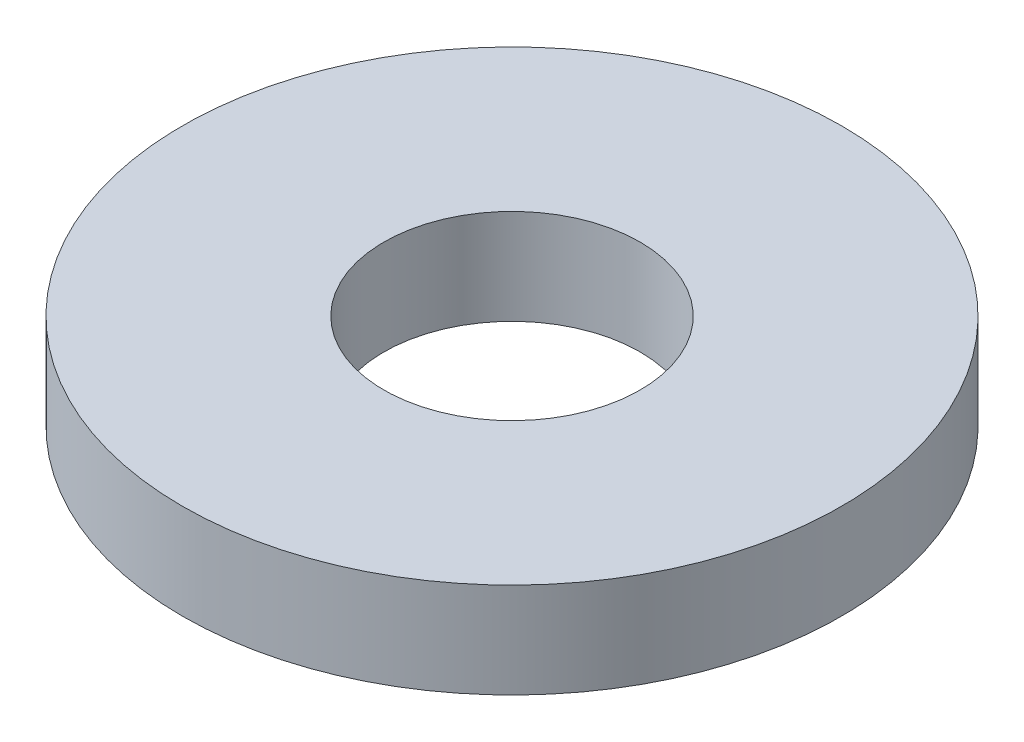
SolidWorks part; units mm, degrees
ref_plane "Front Plane" through (0, 0, 0) normal (0, 0, 1) x (1, 0, 0)
ref_plane "Top Plane" through (0, 0, 0) normal (0, 1, 0) x (1, 0, 0)
ref_plane "Right Plane" through (0, 0, 0) normal (1, 0, 0) x (0, 0, -1)
sketch "Sketch1" plane through (0, 0, 0) normal (0, 1, 0) x (1, 0, 0)
  circle A0 centre (0, 0) radius 90
  dimension "FLANGE_OD" = 180
extrude "Boss-Extrude1" add sketch "Sketch1" along normal blind 26
sketch "Sketch2" plane through (0, 0, 0) normal (0, 1, 0) x (1, 0, 0)
  circle A0 centre (0, 0) radius 35
  dimension "BORE_D" = 70
extrude "Cut-Extrude1" cut sketch "Sketch2" along normal through all
sketch "Sketch3" plane through (0, 26, 0) normal (0, 1, 0) x (1, 0, 0)
  circle A0 centre (0, 0) radius 23.7628 construction
  circle A1 centre (-23.7628, 0) radius 8.3193
  dimension "BOLT_D" = 16.6386
  dimension "BOLT_PCD" = 47.5257
extrude "Cut-Extrude2" cut sketch "Sketch3" against normal blind 16.2054 rebuild error yes
pattern_circular "CirPattern1" count 4 over 360 rebuild error yes
